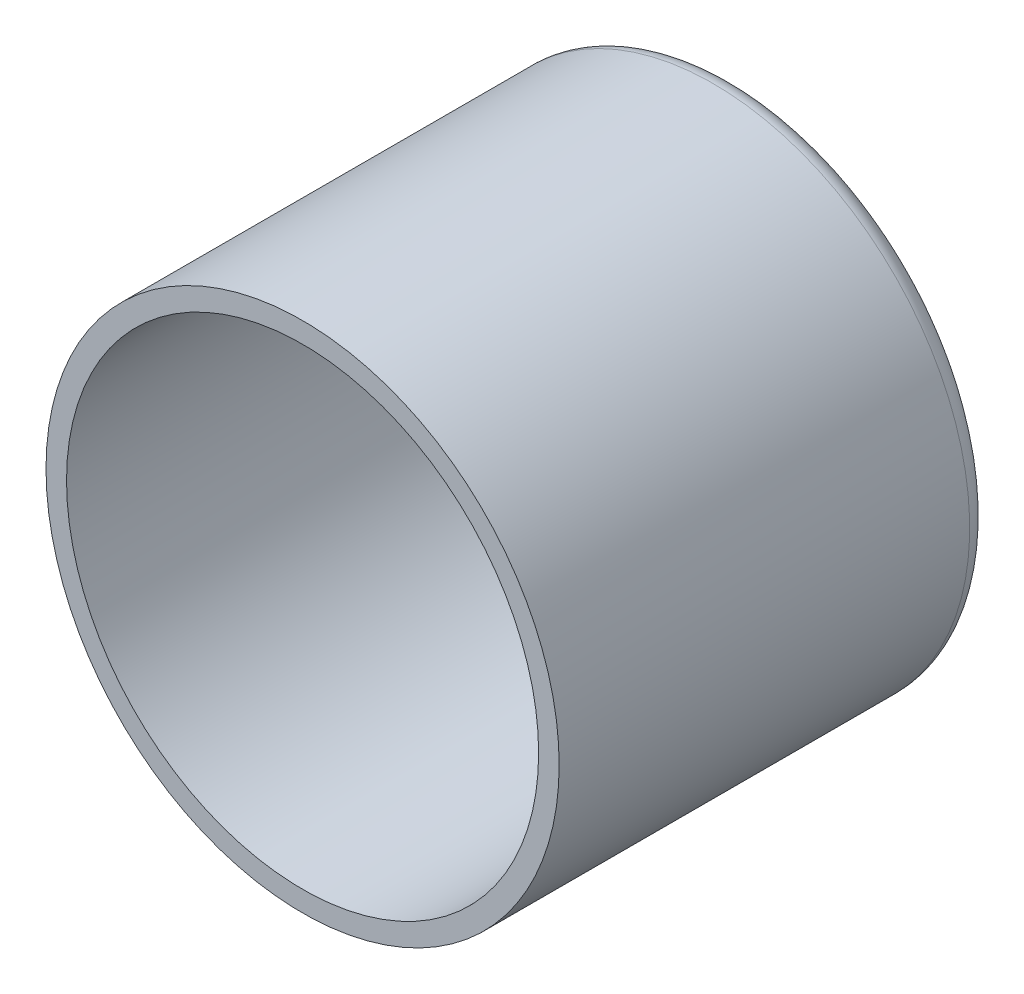
SolidWorks part; units mm, degrees
ref_plane "前视基准面" through (0, 0, 0) normal (0, 0, 1) x (1, 0, 0)
ref_plane "上视基准面" through (0, 0, 0) normal (0, 1, 0) x (1, 0, 0)
ref_plane "右视基准面" through (0, 0, 0) normal (1, 0, 0) x (0, 0, -1)
sketch "草图1" plane through (0, 0, 0) normal (0, 0, 1) x (1, 0, 0)
  circle A0 centre (0, 0) radius 23
  circle A1 centre (0, 0) radius 25
extrude "凸台-拉伸1" add sketch "草图1" along normal blind 40
sketch "草图2" plane through (0, 0, 0) normal (0, 0, -1) x (-1, 0, 0)
  circle A0 centre (0, 0) radius 25
extrude "凸台-拉伸2" add sketch "草图2" along normal blind 2
sketch "草图3" plane through (0, 0, -2) normal (0, 0, -1) x (-1, 0, 0)
  circle A0 centre (0, 0) radius 16.5
extrude "切除-拉伸1" cut sketch "草图3" against normal blind 2
fillet "圆角1" radius 2 1 edges at (-25, 0, -2)
fillet "圆角2" radius 2 1 edges at (23, 0, 0)
fillet "圆角3" radius 2 1 edges at (-16.5, 0, -2)
